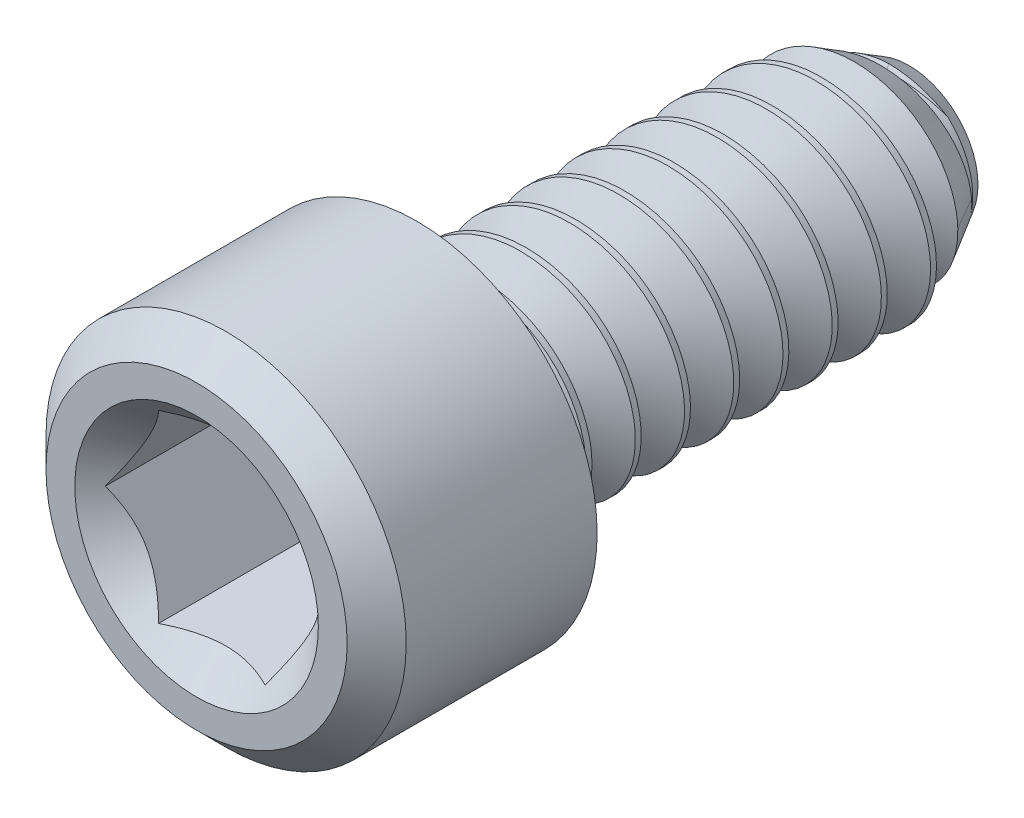
SolidWorks part; units mm, degrees
ref_plane "Front Plane" through (0, 0, 0) normal (0, 0, 1) x (1, 0, 0)
ref_plane "Top Plane" through (0, 0, 0) normal (0, 1, 0) x (1, 0, 0)
ref_plane "Right Plane" through (0, 0, 0) normal (1, 0, 0) x (0, 0, -1)
sketch "Sketch2" plane through (0, 0, 0) normal (0, 0, 1) x (1, 0, 0)
  circle A0 centre (0, 0) radius 1.4224
  dimension "D1" = 2.8448
curve "Helix/Spiral1" pitch 0.635 height 40.64 radius 1.4224 centre (0, 0, 0) axis (0, 0, 1) start towards (0, 1, 0) parameters "TPI LENGTH"=40.64, "PITCH"=0.635
sketch "Sketch3" plane through (0, 0, 0) normal (1, 0, 0) x (0, 0, -1)
  line L0 (0.0381, 1.4224) -> (-0.0381, 1.4224)
  line L1 (-0.0381, 1.4224) -> (-0.2921, 0.9825)
  line L2 (-0.2921, 0.9825) -> (0.2921, 0.9825)
  line L3 (0.2921, 0.9825) -> (0.0381, 1.4224)
  line L4 (0, 0) -> (0, 1.4224) construction
  line L5 (-0.1651, 1.2024) -> (0.1651, 1.2024) construction
  line L6 (0, 1.4224) -> (0, -1.4224) construction
  line L7 (0, 1.4884) -> (0.3302, 1.4884) construction
  line L8 (0.3302, 1.4884) -> (0.3302, 0.9165) construction
  line L9 (0.3302, 0.9165) -> (1.6596, 3.2191) construction
  line L10 (-0.9361, 1.4224) -> (-0.9361, 0.9825) construction
  dimension "D1" = 60
  dimension "D2" = 30
  dimension "D3" = 0.5719
  dimension "pitch*.125" = 0.0762
  dimension "D4" = 0.4399
  dimension "pitch*.5" = 0.3302
  dimension "1/2pitch" = 0.3302
sweep "Sweep1" add profiles "Sketch3" path "Helix/Spiral1"
sketch "Sketch22" plane through (0, 0, 0) normal (1, 0, 0) x (0, 0, -1)
  line L0 (0.0381, 1.4224) -> (-0.0381, 1.4224) construction
  line L1 (0.0381, 1.4224) -> (-0.0381, 1.4224)
sketch "Sketch4" plane through (0, 0, 0) normal (1, 0, 0) x (0, 0, -1)
  line L0 (-1.9435, 0.508) -> (0.436, 0.508) construction
  line L4 (0.2921, 0.9825) -> (0.0381, 1.4224)
  line L5 (-0.2921, 0.9825) -> (0.2921, 0.9825)
  line L6 (-0.0381, 1.4224) -> (-0.2921, 0.9825)
  line L7 (0.0381, 1.4224) -> (-0.0381, 1.4224)
  line L8 (0.2921, 0.9825) -> (0.0381, 1.4224)
  line L9 (-0.2921, 0.9825) -> (0.2921, 0.9825)
  line L10 (-0.0381, 1.4224) -> (-0.2921, 0.9825)
  line L11 (0.0381, 1.4224) -> (-0.0381, 1.4224)
  dimension "D2" = 0.508
  dimension "D1" = 0
revolve "Revolve1" add sketch "Sketch4" angle 360 about L0
sketch "Sketch5" plane through (0, 0, 0) normal (1, 0, 0) x (0, 0, -1)
  line L0 (0, 0) -> (3.5657, 0) construction
  line L2 (0, 0) -> (-40.9321, 0)
  line L3 (0, 0) -> (0, 0.9825)
  line L4 (0, 0.9825) -> (-40.9321, 0.9825)
  line L5 (-40.9321, 0) -> (-40.9321, 0.9825)
revolve "Revolve2" add sketch "Sketch5" angle 360 about L0
sketch "Sketch7" plane through (0, 0, 0) normal (1, 0, 0) x (0, 0, -1)
  line L0 (0, 0.889) -> (-3.7395, 3.048)
  line L1 (-3.7395, 3.048) -> (0.762, 3.048)
  line L2 (0.762, 3.048) -> (0.762, 0)
  line L3 (0, 0.889) -> (0, 0)
  line L4 (0, 0) -> (0.762, 0)
  line L5 (0, 0) -> (11.6435, 0) construction
  dimension "D1" = 30
  dimension "D2" = 0.889
  dimension "D3" = 3.048
  dimension "D4" = 0.762
revolve "Cut-Revolve1" cut sketch "Sketch7" angle 360 about L5
sketch "Sketch10" plane through (0, 0, 0) normal (1, 0, 0) x (0, 0, -1)
  line L0 (0, 2.5565) -> (0, -2.5565) construction
  line L1 (-82.55, -9.525) -> (-6.35, -9.525)
  line L2 (-82.55, -9.525) -> (-82.55, 9.525)
  line L3 (-82.55, 9.525) -> (-6.35, 9.525)
  line L4 (-6.35, -9.525) -> (-6.35, 9.525)
  line L6 (-6.35, 0) -> (-21.2921, 0) construction
  line L7 (2.5565, 0) -> (-2.5565, 0) construction
  point P7 (0, 0)
  dimension "D1" = 76.2
  dimension "D2" = 6.35
  dimension "D3" = 19.05
extrude "Cut-Extrude3" cut sketch "Sketch10" against normal through all and the other way through all
sketch "Sketch17" plane through (0, 0, 6.35) normal (0, 0, 1) x (1, 0, 0)
  circle A0 centre (0, 0) radius 2.3241
  dimension "D1" = 4.6482
extrude "Extrude2" add sketch "Sketch17" along normal blind 12.7
sketch "Sketch18" plane through (0, 0, 0) normal (1, 0, 0) x (0, 0, -1)
  line L0 (0, 0) -> (-21.4476, 0) construction
  line L1 (-6.35, 2.3241) -> (-19.05, 2.3241) construction
  line L2 (-6.35, -2.3241) -> (-6.35, 2.3241) construction
  line L3 (-19.05, 2.3241) -> (-19.05, -2.3241) construction
  line L4 (-9.1948, 0) -> (-9.1948, 2.3241)
  line L5 (-9.1948, 2.3241) -> (-19.304, 2.3241)
  line L6 (-19.304, 2.3241) -> (-19.304, 0)
  line L7 (-19.304, 0) -> (-9.1948, 0)
  dimension "D2" = 2.8448
  dimension "D3" = 0.254
revolve "Cut-Revolve3" cut sketch "Sketch18" angle 360 about L0
sketch "Sketch19" plane through (0, 0, 9.1948) normal (0, 0, 1) x (1, 0, 0)
  line L1 (0.6874, -1.1906) -> (1.3748, 0)
  line L2 (1.3748, 0) -> (0.6874, 1.1906)
  line L3 (0.6874, 1.1906) -> (-0.6874, 1.1906)
  line L4 (-0.6874, 1.1906) -> (-1.3748, 0)
  line L5 (-1.3748, 0) -> (-0.6874, -1.1906)
  line L6 (-0.6874, -1.1906) -> (0.6874, -1.1906)
  circle A0 centre (0, 0) radius 1.1906 construction
  dimension "D1" = 2.3813
extrude "Cut-Extrude4" cut sketch "Sketch19" against normal blind 2.032
sketch "Sketch20" plane through (0, 0, 0) normal (-1, 0, 0) x (0, 1, 0)
  line L0 (-1.1906, -7.1628) -> (-1.1906, -9.1948) construction
  line L1 (0, -10.3089) -> (0, 1.1556) construction
  line L2 (0, 0) -> (0, -40.9321) construction
  line L3 (0, 0) -> (0, 3.5657) construction
  line L4 (-1.5716, -9.1948) -> (-1.1906, -8.8138)
  line L6 (-2.3241, -9.1948) -> (2.3241, -9.1948) construction
  line L7 (-1.1906, -8.8138) -> (-1.1906, -7.1628)
  line L8 (-1.1906, -7.1628) -> (0, -6.4474)
  line L9 (0, -6.4474) -> (0, -9.1948)
  line L10 (0, -9.1948) -> (-1.5716, -9.1948)
  line L11 (0, -7.1628) -> (-1.1906, -7.1628) construction
  dimension "D1" = 59
  dimension "D2" = 45
  dimension "D3" = 0.381
revolve "Cut-Revolve5" cut sketch "Sketch20" angle 360 about L1
chamfer "Chamfer1" distance 0.381 angle 45 1 edges at (-2.3241, 0, 9.1948)
